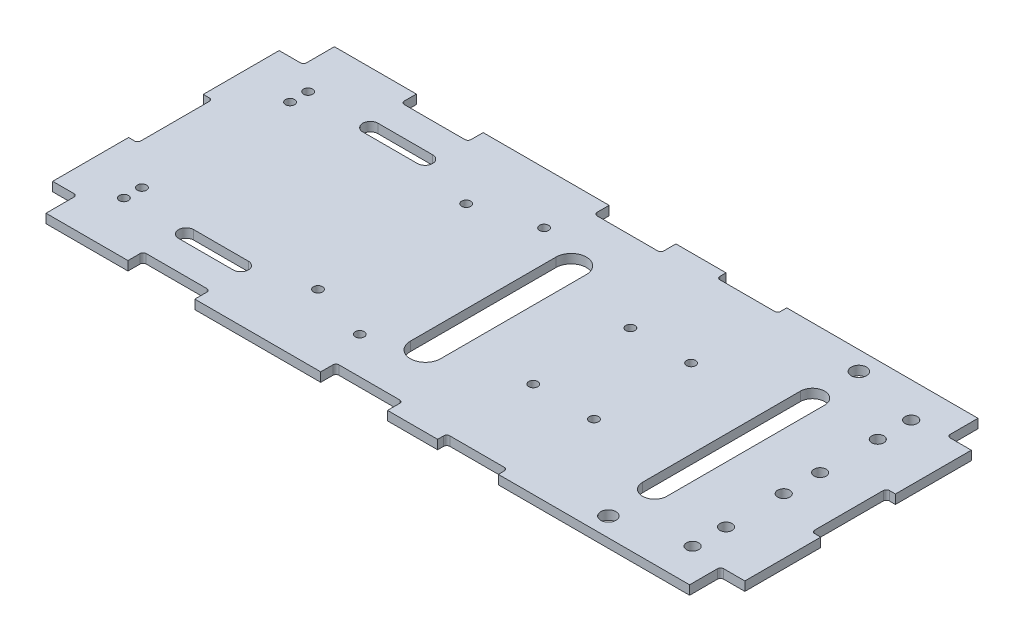
SolidWorks part; units mm, degrees
ref_plane "前视" through (0, 0, 0) normal (0, 0, 1) x (1, 0, 0)
ref_plane "上视" through (0, 0, 0) normal (0, 1, 0) x (1, 0, 0)
ref_plane "右视" through (0, 0, 0) normal (1, 0, 0) x (0, 0, -1)
sketch "草图4" plane through (0, 0, 0) normal (0, 1, 0) x (1, 0, 0)
  line L1 (-114, 47.5) -> (114, 47.5)
  line L2 (-114, 47.5) -> (-114, -47.5)
  line L3 (-114, -47.5) -> (114, -47.5)
  line L4 (114, 47.5) -> (114, -47.5)
  line L5 (-114, 47.5) -> (114, -47.5) construction
  line L6 (-114, -47.5) -> (114, 47.5) construction
  point P0 (0, 0)
  dimension "D1" = 228
  dimension "D2" = 95
extrude "凸台-拉伸3" add sketch "草图4" along normal blind 3
sketch "草图5" plane through (0, 3, 0) normal (0, 1, 0) x (1, 0, 0)
  line L0 (-123.3795, 0) -> (123.3795, 0) construction
  line L1 (-114, 0) -> (-111, 0)
  line L2 (-114, 47.5) -> (-114, -47.5) construction
  line L3 (-111, 0) -> (-111, 12.3)
  line L4 (-111, 12.3) -> (-114, 12.3)
  line L5 (-114, 12.3) -> (-114, 0)
  dimension "D1" = 3
  dimension "D2" = 12.3
extrude "切除-拉伸1" cut sketch "草图5" against normal through all
sketch "草图6" plane through (0, 3, 0) normal (0, 1, 0) x (1, 0, 0)
  line L0 (-131.3489, 37.3) -> (-63.4026, 37.3) construction
  line L1 (-111, 12.3) -> (-114, 12.3) construction
  line L2 (-114, 37.3) -> (-106, 37.3)
  line L3 (-114, 47.5) -> (-114, 12.3) construction
  line L4 (-106, 37.3) -> (-106, 47.5)
  line L5 (114, 47.5) -> (-114, 47.5) construction
  line L6 (-106, 47.5) -> (-114, 47.5)
  line L7 (-114, 47.5) -> (-114, 37.3)
  point P2 (-112.5, 12.3)
  dimension "D1" = 25
  dimension "D2" = 8
extrude "切除-拉伸2" cut sketch "草图6" against normal through all
fillet "圆角2" radius 1 1 edges at (-106, 1.5, -37.3)
fillet "圆角5" radius 1 1 edges at (-111, 1.5, -12.3)
sketch "草图7" plane through (0, 3, 0) normal (0, 1, 0) x (1, 0, 0)
  line L0 (-124.891, 0) -> (8.2781, 0) construction
  line L1 (-114, 0) -> (-111, 0)
  line L2 (-111, 0) -> (-111, -12.3)
  line L3 (-111, -12.3) -> (-114, -12.3)
  line L4 (-114, 0) -> (-114, -47.5) construction
  line L5 (-114, -12.3) -> (-114, 0)
  dimension "D1" = 12.3
extrude "切除-拉伸3" cut sketch "草图7" against normal through all
fillet "圆角6" radius 1 1 edges at (-111, 1.5, 12.3)
sketch "草图8" plane through (0, 3, 0) normal (0, 1, 0) x (1, 0, 0)
  line L0 (0, 0) -> (-144.9788, 0) construction
  line L1 (-144.9788, -37.3) -> (0, -37.3) construction
  line L2 (-114, -37.3) -> (-106, -37.3)
  line L3 (-106, -37.3) -> (-106, -47.5)
  line L4 (-114, -47.5) -> (114, -47.5) construction
  line L5 (-106, -47.5) -> (-114, -47.5)
  line L6 (-114, -37.3) -> (-114, -47.5)
  dimension "D1" = 37.3
  dimension "D2" = 8
extrude "切除-拉伸5" cut sketch "草图8" against normal through all
fillet "圆角9" radius 1 1 edges at (-106, 1.5, 37.3)
sketch "草图10" plane through (0, 3, 0) normal (0, 1, 0) x (1, 0, 0)
  line L0 (134.5344, 0) -> (0, 0) construction
  line L1 (114, 0) -> (111, 0)
  line L2 (111, 0) -> (111, 12.3)
  line L3 (111, 12.3) -> (114, 12.3)
  line L4 (114, -47.5) -> (114, 47.5) construction
  line L5 (114, 12.3) -> (114, 0)
  dimension "D1" = 12.3
  dimension "D2" = 3
extrude "切除-拉伸6" cut sketch "草图10" against normal through all
sketch "草图11" plane through (0, 3, 0) normal (0, 1, 0) x (1, 0, 0)
  line L0 (115.7031, 0) -> (0, 0) construction
  line L1 (114, 0) -> (111, 0)
  line L2 (111, 0) -> (111, -12.3)
  line L3 (111, -12.3) -> (114, -12.3)
  line L4 (114, -47.5) -> (114, 0) construction
  line L5 (114, -12.3) -> (114, 0)
  dimension "D1" = 12.3
extrude "切除-拉伸7" cut sketch "草图11" against normal through all
sketch "草图12" plane through (0, 3, 0) normal (0, 1, 0) x (1, 0, 0)
  line L0 (121.1687, 0) -> (0, 0) construction
  line L1 (138.0658, 37.3) -> (0, 37.3) construction
  line L2 (114, 37.3) -> (106, 37.3)
  line L3 (114, 12.3) -> (114, 47.5) construction
  line L4 (106, 37.3) -> (106, 47.5)
  line L5 (114, 47.5) -> (-106, 47.5) construction
  line L6 (106, 47.5) -> (114, 47.5)
  line L7 (114, 47.5) -> (114, 37.3)
  dimension "D1" = 37.3
  dimension "D2" = 8
extrude "切除-拉伸8" cut sketch "草图12" against normal through all
sketch "草图13" plane through (0, 3, 0) normal (0, 1, 0) x (1, 0, 0)
  line L0 (116.1404, 0) -> (0, 0) construction
  line L1 (0, -37.3) -> (128.8835, -37.3) construction
  line L2 (114, -47.5) -> (114, -37.3)
  line L3 (114, -47.5) -> (106, -47.5)
  line L4 (-106, -47.5) -> (114, -47.5) construction
  line L5 (106, -47.5) -> (106, -37.3)
  line L6 (114, -37.3) -> (106, -37.3)
  line L7 (114, -47.5) -> (114, -12.3) construction
  dimension "D1" = 37.3
  dimension "D2" = 8
extrude "切除-拉伸10" cut sketch "草图13" against normal through all
fillet "圆角13" radius 1 1 edges at (106, 1.5, -37.3)
fillet "圆角15" radius 1 1 edges at (106, 1.5, 37.3)
fillet "圆角18" radius 1 1 edges at (111, 1.5, 12.3)
fillet "圆角19" radius 1 1 edges at (111, 1.5, -12.3)
sketch "草图14" plane through (0, 3, 0) normal (0, 1, 0) x (1, 0, 0)
  line L0 (-120.6789, 0) -> (128.866, 0) construction
  line L1 (-76.996, 30.35) -> (-58.996, 30.35) construction
  line L2 (-4.5, 24) -> (-4.5, -24) construction
  line L3 (0.5, 24) -> (0.5, -24)
  line L4 (-9.5, 24) -> (-9.5, -24)
  line L5 (111, 11.3) -> (111, -11.3) construction
  line L6 (73, 26) -> (73, -26) construction
  line L7 (77, 26) -> (77, -26)
  line L8 (69, 26) -> (69, -26)
  line L9 (-76.996, 32.85) -> (-58.996, 32.85)
  line L10 (-114, 37.3) -> (-114, 12.3) construction
  line L11 (-76.996, 27.85) -> (-58.996, 27.85)
  line L12 (106, 47.5) -> (-106, 47.5) construction
  line L14 (-78.996, 52.5) -> (-56.996, 52.5)
  line L15 (-78.996, 52.5) -> (-78.996, 42.5)
  line L16 (-78.996, 42.5) -> (-56.996, 42.5)
  line L17 (-56.996, 52.5) -> (-56.996, 42.5)
  line L18 (-78.996, 52.5) -> (-56.996, 42.5) construction
  line L19 (-78.996, 42.5) -> (-56.996, 52.5) construction
  line L20 (43, -50.5) -> (43, -44.5)
  line L21 (-15.5, 52.5) -> (6.5, 52.5)
  line L22 (-15.5, 52.5) -> (-15.5, 42.5)
  line L23 (-15.5, 42.5) -> (6.5, 42.5)
  line L24 (6.5, 52.5) -> (6.5, 42.5)
  line L25 (-15.5, 52.5) -> (6.5, 42.5) construction
  line L26 (-15.5, 42.5) -> (6.5, 52.5) construction
  line L27 (23, 50.5) -> (43, 50.5)
  line L28 (-76.996, -30.35) -> (-58.996, -30.35) construction
  line L29 (-76.996, -32.85) -> (-58.996, -32.85)
  line L30 (-76.996, -27.85) -> (-58.996, -27.85)
  line L31 (23, 50.5) -> (23, 44.5)
  line L32 (23, 44.5) -> (43, 44.5)
  line L33 (43, 50.5) -> (43, 44.5)
  line L34 (23, 50.5) -> (43, 44.5) construction
  line L35 (23, 44.5) -> (43, 50.5) construction
  line L36 (23, -50.5) -> (43, -50.5)
  line L37 (23, -50.5) -> (23, -44.5)
  line L38 (23, -44.5) -> (43, -44.5)
  line L39 (-15.5, -52.5) -> (6.5, -52.5)
  line L40 (-15.5, -52.5) -> (-15.5, -42.5)
  line L41 (6.5, -52.5) -> (6.5, -42.5)
  line L42 (-15.5, -42.5) -> (6.5, -42.5)
  line L43 (-78.996, -52.5) -> (-56.996, -52.5)
  line L44 (-78.996, -52.5) -> (-78.996, -42.5)
  line L45 (-78.996, -42.5) -> (-56.996, -42.5)
  line L46 (-56.996, -52.5) -> (-56.996, -42.5)
  circle A0 centre (-97.5, 30.35) radius 1.5
  circle A1 centre (-19.78, 30.35) radius 1.5
  circle A2 centre (-97.5, 24.4) radius 1.5
  circle A3 centre (-39.5, 24.4) radius 1.5
  arc A4 (0.5, 24) -> (-9.5, 24) centre (-4.5, 24) ccw
  arc A5 (-9.5, -24) -> (0.5, -24) centre (-4.5, -24) ccw
  circle A6 centre (95.5, 6) radius 2
  circle A7 centre (95.5, 25) radius 2
  circle A8 centre (95.5, 36) radius 2
  circle A9 centre (73, 41.25) radius 2.5
  circle A10 centre (43, 16) radius 1.5
  circle A11 centre (23, 16) radius 1.5
  arc A12 (77, 26) -> (69, 26) centre (73, 26) ccw
  arc A13 (69, -26) -> (77, -26) centre (73, -26) ccw
  arc A14 (-76.996, 32.85) -> (-76.996, 27.85) centre (-76.996, 30.35) ccw
  arc A15 (-58.996, 27.85) -> (-58.996, 32.85) centre (-58.996, 30.35) ccw
  circle A22 centre (95.5, -6) radius 2
  circle A23 centre (95.5, -25) radius 2
  circle A24 centre (95.5, -36) radius 2
  circle A25 centre (73, -41.25) radius 2.5
  circle A28 centre (43, -16) radius 1.5
  circle A29 centre (23, -16) radius 1.5
  circle A32 centre (-19.78, -30.35) radius 1.5
  circle A33 centre (-39.5, -24.4) radius 1.5
  arc A34 (-76.996, -32.85) -> (-76.996, -27.85) centre (-76.996, -30.35) cw
  arc A35 (-58.996, -27.85) -> (-58.996, -32.85) centre (-58.996, -30.35) cw
  circle A38 centre (-97.5, -24.4) radius 1.5
  circle A39 centre (-97.5, -30.35) radius 1.5
  point P15 (-4.5, 0)
  point P36 (73, 0)
  point P43 (-67.996, 30.35)
  point P48 (-67.996, 47.5)
  point P55 (-4.5, 47.5)
  point P60 (33, 47.5)
  point P103 (-67.996, -30.35)
  dimension "D1" = 30.35
  dimension "D3" = 3
  dimension "D4" = 30.35
  dimension "D6" = 3
  dimension "D8" = 58
  dimension "D13" = 6
  dimension "D15" = 25
  dimension "D16" = 36
  dimension "D17" = 38
  dimension "D19" = 16
  dimension "D21" = 50
  dimension "D25" = 3
  dimension "D26" = 3
  dimension "D27" = 30.35
  dimension "D30" = 22
  dimension "D33" = 10
  dimension "D36" = 137
  dimension "D5" = 77.72
  dimension "D7" = 24.4
  dimension "D9" = 93
  dimension "D10" = 10
  dimension "D11" = 16.5
  dimension "D12" = 48
  dimension "D14" = 15.5
  dimension "D18" = 41.25
  dimension "D20" = 30
  dimension "D22" = 8
  dimension "D23" = 52
  dimension "D24" = 16.5
  dimension "D28" = 5
  dimension "D29" = 46.004
  dimension "D31" = 10
  dimension "D32" = 22
  dimension "D34" = 20
  dimension "D35" = 6
extrude "切除-拉伸11" cut sketch "草图14" against normal through all
fillet "圆角20" radius 1 1 edges at (-78.996, 1.5, -42.5)
fillet "圆角21" radius 1 1 edges at (-56.996, 1.5, -42.5)
fillet "圆角22" radius 1 1 edges at (-15.5, 1.5, -42.5)
fillet "圆角23" radius 1 1 edges at (6.5, 1.5, -42.5)
fillet "圆角24" radius 1 1 edges at (23, 1.5, -44.5)
fillet "圆角25" radius 1 1 edges at (43, 1.5, -44.5)
fillet "圆角26" radius 1 1 edges at (-78.996, 1.5, 42.5)
fillet "圆角27" radius 1 1 edges at (-56.996, 1.5, 42.5)
fillet "圆角28" radius 1 1 edges at (-15.5, 1.5, 42.5)
fillet "圆角29" radius 1 1 edges at (6.5, 1.5, 42.5)
fillet "圆角30" radius 1 1 edges at (23, 1.5, 44.5)
fillet "圆角31" radius 1 1 edges at (43, 1.5, 44.5)
